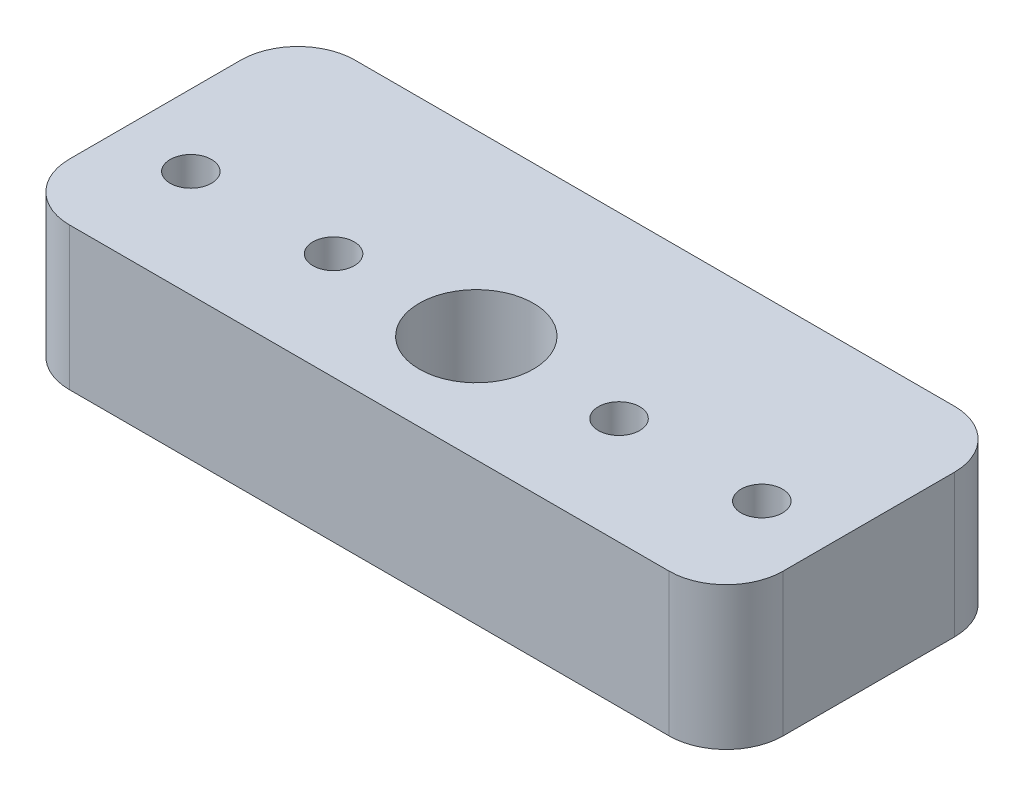
SolidWorks part; units mm, degrees
ref_plane "Front Plane" through (0, 0, 0) normal (0, 0, 1) x (1, 0, 0)
ref_plane "Top Plane" through (0, 0, 0) normal (0, 1, 0) x (1, 0, 0)
ref_plane "Right Plane" through (0, 0, 0) normal (1, 0, 0) x (0, 0, -1)
sketch "Sketch1" plane through (0, 0, 0) normal (0, 1, 0) x (1, 0, 0)
  line L0 (-25, -2.5) -> (25, -2.5) construction
  line L1 (-21, 10) -> (21, 10)
  line L2 (-25, 6) -> (-25, -6)
  line L3 (-21, -10) -> (21, -10)
  line L4 (25, 6) -> (25, -6)
  line L5 (-25, 10) -> (25, -10) construction
  line L6 (-25, -10) -> (25, 10) construction
  line L7 (0, -10) -> (0, 10) construction
  line L8 (25, 10) -> (-25, -10) construction
  arc A0 (-25, -6) -> (-21, -10) centre (-21, -6) ccw
  arc A1 (21, -10) -> (25, -6) centre (21, -6) ccw
  arc A2 (21, 10) -> (25, 6) centre (21, 6) cw
  arc A3 (-21, 10) -> (-25, 6) centre (-21, 6) ccw
  circle A4 centre (0, -2.5) radius 4
  circle A5 centre (10, -2.5) radius 1.45
  circle A6 centre (20, -2.5) radius 1.45
  circle A7 centre (-20, -2.5) radius 1.45
  circle A8 centre (-10, -2.5) radius 1.45
  point P0 (0, 0)
  dimension "D3" = 4
  dimension "D4" = 8
  dimension "D5" = 2.9
  dimension "D6" = 2.9
  dimension "D1" = 20
  dimension "D7" = 7.5
  dimension "D8" = 10
  dimension "D9" = 40
  dimension "D2" = 5
extrude "Boss-Extrude1" add sketch "Sketch1" along normal blind 10
equation "\"Y-ROD-SPACING\"=75"
equation "\"Y-BED-OFFSET\"=2"
equation "\"Y-BED-ROD-INSET\"=3.5"
equation "\"T-SLOT-NUT-FILLET-RADIUS\"=0.5"
equation "\"T-SLOT-SCREW-SHAFT-RADIUS\"=1.55"
equation "\"T-SLOT-SCREW-SHAFT-CUTOUT-LENGTH\"=11"
equation "\"T-SLOT-NUT-DEPTH\"=3.5"
equation "\"T-SLOT-NUT-WIDTH\"=2.85"
equation "\"T-SLOT-NUT-END-DISTANCE\"=8"
equation "\"ACRYLIC-TAB-CUTOUT-SIZE\"=\"ACRYLIC-THICKNESS\"+\"ACRYLIC-TAB-TOLERANCE\"*2"
equation "\"ACRYLIC-M3-HOLE\"=2.9"
equation "\"SMOOTHROD-CAP-SCREW-DISTANCE\"=20"
equation "\"D5@Sketch1\"=\"ACRYLIC-M3-HOLE\""
equation "\"D6@Sketch1\"=\"ACRYLIC-M3-HOLE\""
equation "\"D8@Sketch1\"=\"SMOOTHROD-CAP-SCREW-DISTANCE\"/2"
equation "\"ACRYLIC-TAB-WIDTH\"=\"ACRYLIC-THICKNESS\""
equation "\"FRAME-WIDTH-INNER\"=370"
equation "\"NEMA17-HOLE-SPACING\"=31"
equation "\"NEMA17-CENTRAL-CUTOUT\"=22.5"
equation "\"Z-BRACKET-REACH\"=55"
equation "\"TOP-BRACKET-SPACING\"=40"
equation "\"D9@Sketch1\"=\"TOP-BRACKET-SPACING\""
equation "\"D2@Sketch1\"=\"ACRYLIC-TAB-WIDTH\"/2"
equation "\"X-ROD-SPACING\"=45"
equation "\"Z-ROD-SPACING\"=17.5"
equation "\"ACRYLIC-THICKNESS\"=10"
equation "\"ACRYLIC-THICKNESS2\"=4.5"
equation "\"SMOOTHROD-X-LENGTH\"=350"
equation "\"SMOOTHROD-Y-LENGTH\"=350"
equation "\"SMOOTHROD-Z-LENGTH\"=350"
equation "\"SMOOTHROD-TIGHTENING-HEADROOM\"=.25"
equation "\"LEADSCREW-Z-LENGTH\"=300"
equation "\"SCREW-LENGTH-FRAME\"=\"ACRYLIC-THICKNESS\" + 10"
equation "\"SCREW-HEAD-RADIUS\"=6"
equation "\"PRINTED-X-SMOOTHROD-DIAMETER\"=8.8"
equation "\"PRINTED-X-SMOOTHROD-CUTOUT\"=10"
equation "\"PRINTED-X-BASE-HEIGHT\"=10"
equation "\"PRINTED-LM8UU-CUTOUT-SIZE\"=15.5"
equation "\"PRINTED-LM8UU-CUTOUT-LENGTH\"=24.5"
equation "\"PRINTED-X-IDLER-HEIGHT\"=16"
equation "\"PSU-MOUNTING-WIDTH\"=95"
equation "\"PSU-MOUNTING-HEIGHT\"=177"
equation "\"D1@Boss-Extrude1\"=\"ACRYLIC-THICKNESS\""
